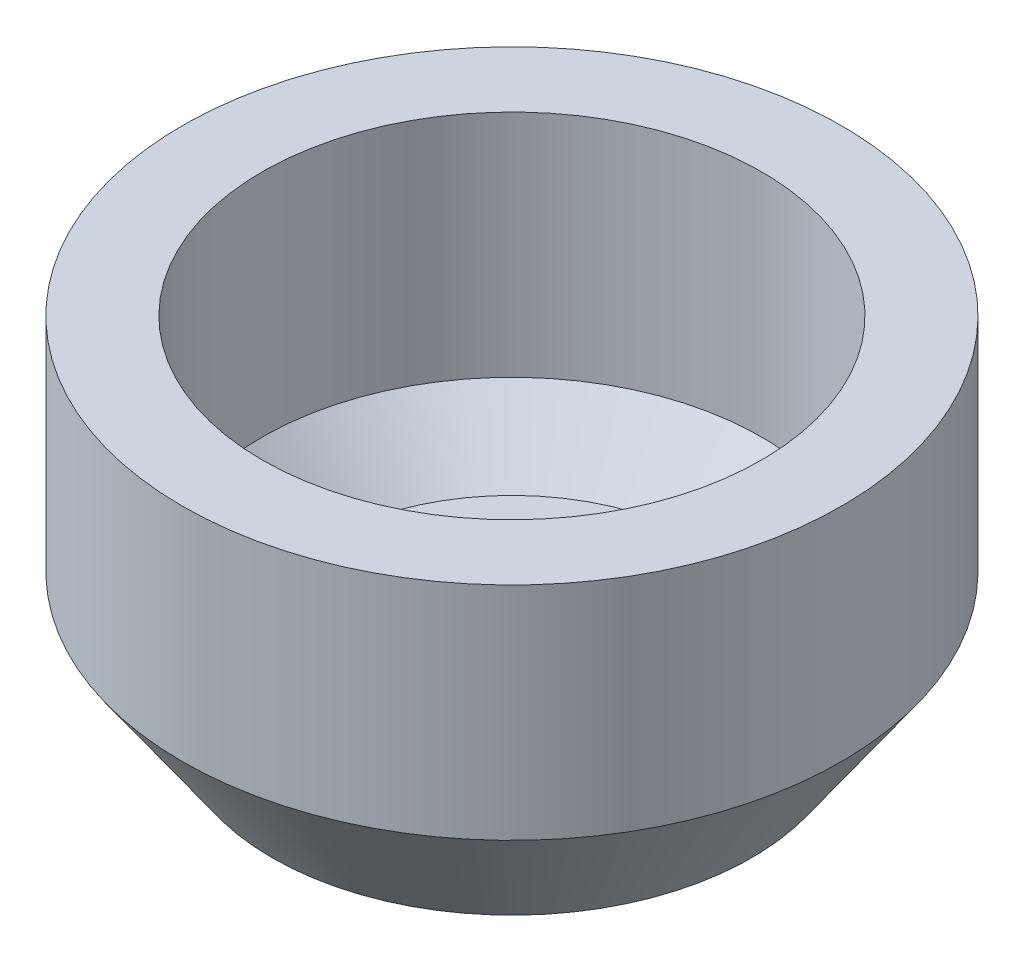
SolidWorks part; units mm, degrees
ref_plane "Front Plane" through (0, 0, 0) normal (0, 0, 1) x (1, 0, 0)
ref_plane "Top Plane" through (0, 0, 0) normal (0, 1, 0) x (1, 0, 0)
ref_plane "Right Plane" through (0, 0, 0) normal (1, 0, 0) x (0, 0, -1)
sketch "Sketch1" plane through (0, 0, 0) normal (0, 1, 0) x (1, 0, 0)
  circle A0 centre (0, 0) radius 3.3
  circle A1 centre (0, 0) radius 2.5
  dimension "D1" = 6.6
  dimension "D2" = 5
extrude "Boss-Extrude1" add sketch "Sketch1" along normal blind 3.5
extrude "Boss-Extrude2" add sketch "Sketch1<2>" along normal blind 0.6 contours A1
sketch "Sketch1<2>" plane through (0, 0, 0) normal (0, 1, 0) x (1, 0, 0) same geometry as "Sketch1"
sketch "Sketch2" plane through (0, 0, 0) normal (0, 0, 1) x (1, 0, 0)
  line L0 (1.9, 0.6) -> (2.5, 0.6)
  line L1 (2.5, 0.6) -> (-2.5, 0.6) construction
  line L2 (2.5, 0.6) -> (2.5, 1.2)
  line L3 (2.5, 1.2) -> (1.9, 0.6)
  line L4 (0, 0) -> (0, 1.4602) construction
  dimension "D1" = 45
  dimension "D2" = 0.6
  dimension "D3" = 2.5
revolve "Revolve1" add sketch "Sketch2" angle 360 about L4
sketch "Sketch3" plane through (0, 0, 0) normal (0, 0, 1) x (1, 0, 0)
  line L1 (3.7431, 1.9182) -> (3.7431, 0)
  line L3 (3.1, -8.6) -> (-3.1, -8.6)
  line L7 (2.4, 0) -> (3.7431, 0)
  line L9 (2.4, 0) -> (3.7431, 1.9182)
  line L10 (0, 0) -> (0, 1.2529) construction
  line L15 (-3.3, 0) -> (3.3, 0) construction
  dimension "D3" = 1.3431
  dimension "D2" = 2.4
  dimension "D1" = 55
revolve "Cut-Revolve2" cut sketch "Sketch3" angle 360 about L10 region at (3.2954, 0.6394, 0)
